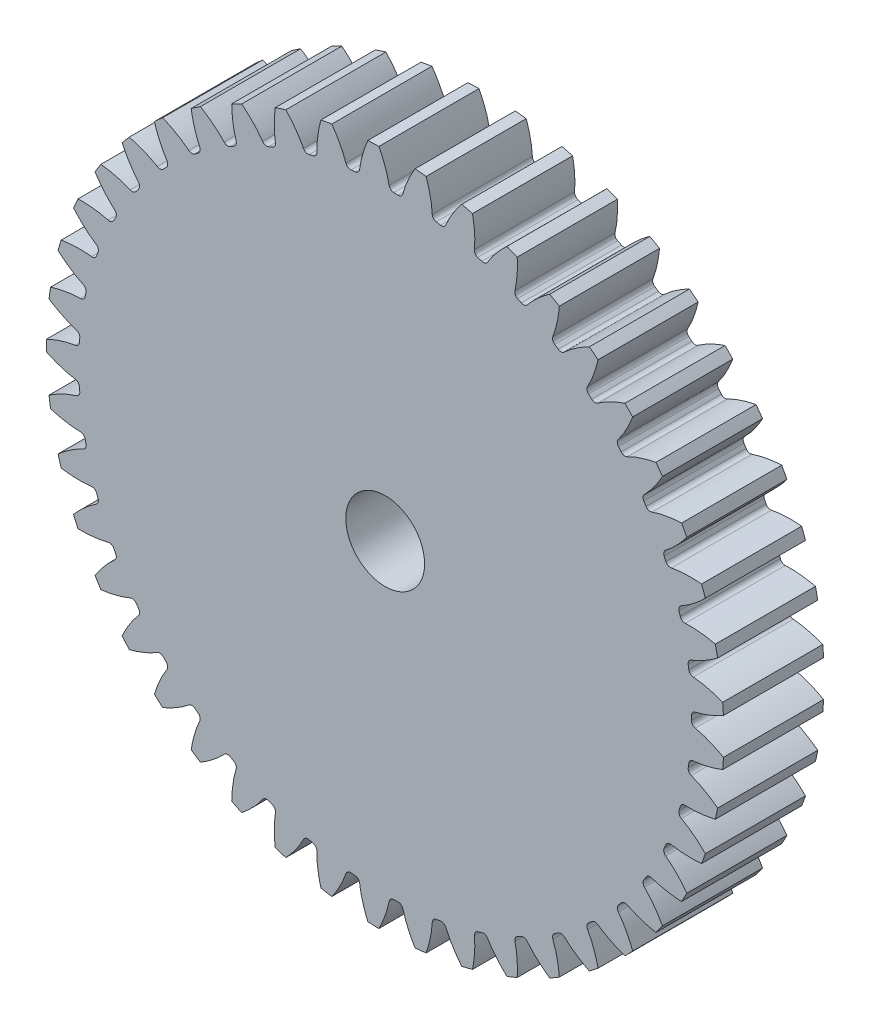
SolidWorks part; units mm, degrees
ref_plane "Front Plane" through (0, 0, 0) normal (0, 0, 1) x (1, 0, 0)
ref_plane "Top Plane" through (0, 0, 0) normal (0, 1, 0) x (1, 0, 0)
ref_plane "Right Plane" through (0, 0, 0) normal (1, 0, 0) x (0, 0, -1)
sketch "Sketch1" plane through (0, 0, 0) normal (0, 0, 1) x (1, 0, 0)
  circle A0 centre (0, 0) radius 21.486
  dimension "D1" = 42.9721
extrude "Boss-Extrude1" add sketch "Sketch1" against normal blind 6.35
sketch "Sketch2" plane through (0, 0, 0) normal (0, 0, 1) x (1, 0, 0)
  line L0 (19.3273, 0.3866) -> (19.425, 0.3886)
  line L1 (19.3273, -0.3866) -> (19.425, -0.3886)
  circle A0 centre (0, 0) radius 21.486
  circle A1 centre (0, 0) radius 19.3311
  circle A2 centre (0, 0) radius 20.5717
  circle A3 centre (0, 0) radius 19.4289
  spline S0 degree 4 poles (19.3273, 0.3866) (19.3364, 0.387) (19.362, 0.3884) (19.4104, 0.393) (19.489, 0.4032) (19.5888, 0.42) (19.7172, 0.4463) (19.8675, 0.4831) (20.0316, 0.5295) (20.2088, 0.5864) (20.3842, 0.6488) (20.5579, 0.7163) (20.7295, 0.7882) (20.9358, 0.8809) (21.1808, 0.9996) (21.4634, 1.1492) (21.7791, 1.3318) (22.0954, 1.5314) (22.402, 1.7388) (22.7059, 1.9608) (22.9958, 2.1844) (23.2906, 2.4289) (23.5594, 2.661) (23.853, 2.9344) (24.0877, 3.1589) (24.3889, 3.469) (24.5642, 3.6563) (24.7664, 3.8801) (24.8545, 3.982) (24.9089, 4.0446) knots 0 0 0 0 0 0.005377 0.015084 0.028532 0.04661 0.064855 0.092111 0.119476 0.146842 0.174209 0.201575 0.228941 0.256307 0.307035 0.361767 0.4165 0.471232 0.525964 0.580697 0.635429 0.690161 0.744894 0.799626 0.854358 0.909091 0.954545 1 1 1 1 1 construction
  spline S1 degree 4 poles (19.3273, 0.3866) (19.3364, 0.387) (19.362, 0.3884) (19.4104, 0.393) (19.489, 0.4032) (19.5888, 0.42) (19.7172, 0.4463) (19.8675, 0.4831) (20.0316, 0.5295) (20.2088, 0.5864) (20.3842, 0.6488) (20.5579, 0.7163) (20.7295, 0.7882) (20.9358, 0.8809) (21.1808, 0.9996) (21.4634, 1.1492) (21.7791, 1.3318) (22.0954, 1.5314) (22.402, 1.7388) (22.7059, 1.9608) (22.9958, 2.1844) (23.2906, 2.4289) (23.5594, 2.661) (23.853, 2.9344) (24.0877, 3.1589) (24.3236, 3.4018) (24.4374, 3.5216) (24.4952, 3.5834) knots 0 0 0 0 0 0.005377 0.015084 0.028532 0.04661 0.064855 0.092111 0.119476 0.146842 0.174209 0.201575 0.228941 0.256307 0.307035 0.361767 0.4165 0.471232 0.525964 0.580697 0.635429 0.690161 0.744894 0.799626 0.854358 0.909091 0.909091 0.909091 0.909091 0.909091
  spline S2 degree 4 poles (19.3273, -0.3866) (19.3364, -0.387) (19.362, -0.3884) (19.4104, -0.393) (19.489, -0.4032) (19.5888, -0.42) (19.7172, -0.4463) (19.8675, -0.4831) (20.0316, -0.5295) (20.2088, -0.5864) (20.3842, -0.6488) (20.5579, -0.7163) (20.7295, -0.7882) (20.9358, -0.8809) (21.1808, -0.9996) (21.4634, -1.1492) (21.7791, -1.3318) (22.0954, -1.5314) (22.402, -1.7388) (22.7059, -1.9608) (22.9958, -2.1844) (23.2906, -2.4289) (23.5594, -2.661) (23.853, -2.9344) (24.0877, -3.1589) (24.3889, -3.469) (24.5642, -3.6563) (24.7664, -3.8801) (24.8545, -3.982) (24.9089, -4.0446) knots 0 0 0 0 0 0.005377 0.015084 0.028532 0.04661 0.064855 0.092111 0.119476 0.146842 0.174209 0.201575 0.228941 0.256307 0.307035 0.361767 0.4165 0.471232 0.525964 0.580697 0.635429 0.690161 0.744894 0.799626 0.854358 0.909091 0.954545 1 1 1 1 1 construction
  spline S3 degree 4 poles (19.3273, -0.3866) (19.3364, -0.387) (19.362, -0.3884) (19.4104, -0.393) (19.489, -0.4032) (19.5888, -0.42) (19.7172, -0.4463) (19.8675, -0.4831) (20.0316, -0.5295) (20.2088, -0.5864) (20.3842, -0.6488) (20.5579, -0.7163) (20.7295, -0.7882) (20.9358, -0.8809) (21.1808, -0.9996) (21.4634, -1.1492) (21.7791, -1.3318) (22.0954, -1.5314) (22.402, -1.7388) (22.7059, -1.9608) (22.9958, -2.1844) (23.2906, -2.4289) (23.5594, -2.661) (23.853, -2.9344) (24.0877, -3.1589) (24.3236, -3.4018) (24.4374, -3.5216) (24.4952, -3.5834) knots 0 0 0 0 0 0.005377 0.015084 0.028532 0.04661 0.064855 0.092111 0.119476 0.146842 0.174209 0.201575 0.228941 0.256307 0.307035 0.361767 0.4165 0.471232 0.525964 0.580697 0.635429 0.690161 0.744894 0.799626 0.854358 0.909091 0.909091 0.909091 0.909091 0.909091
  dimension "D2" = 38.6622
  dimension "D3" = 42.9721
  dimension "D4" = 41.1435
  dimension "D1" = 38.8578
extrude "Cut-Extrude1" cut sketch "Sketch2" against normal up to next contours A2 S3 A0 S1 | A3 S3 A2 S1 region at (20.0564, 0, 0) region at (21.0574, 0, 0)
fillet "Fillet1" radius 0.3068 2 edges at (19.4249, -0.3952, -3.175) (19.4249, 0.3952, -3.175)
pattern_circular "CirPattern1" count 45 over 360 about axis through (0, 0, 0) along (0, 0, 1) of "Cut-Extrude1", "Fillet1"
sketch "Sketch4" plane through (0, 0, 0) normal (0, 0, 1) x (1, 0, 0)
  circle A0 centre (0, 0) radius 2.5
  dimension "D1" = 5
extrude "Cut-Extrude2" cut sketch "Sketch4" against normal up to next
equation "\"Module\"= .9143'module = 25.4/PD"
equation "\"DiametralPitch\"= 25.4 / \"Module\"'DP=25.4/module"
equation "\"NumTeeth\" = 45"
equation "\"PressureAngle\"= 20"
equation "\"Addendum\"= 1 / \"DiametralPitch\""
equation "\"Dedendum\"= 1.25 / \"DiametralPitch\""
equation "\"WorkingDepth\"= 2 / \"DiametralPitch\""
equation "\"WholeDepth\"= 2.25 / \"DiametralPitch\""
equation "\"Clearance\"= 0.25 / \"DiametralPitch\""
equation "\"ToothThickness\"= 1.5708 / \"DiametralPitch\""
equation "\"CircularPitch\"= pi / \"DiametralPitch\""
equation "\"PitchCircle\"= \"NumTeeth\" / \"DiametralPitch\""
equation "\"OutsideDiameter\"= ( \"NumTeeth\" + 2 ) / \"DiametralPitch\""
equation "\"Fillet\"= \"Clearance\" * cos ( \"PressureAngle\" ) * tan ( ( 90 + \"PressureAngle\" ) / 2 )"
equation "\"AddendumCircle\"= \"PitchCircle\" + ( 2 * \"Addendum\" )"
equation "\"DedendumCircle\"= \"PitchCircle\" - ( 2 * \"Dedendum\" )"
equation "\"BaseCircle\"= \"PitchCircle\" * cos ( \"PressureAngle\" )"
equation "\"PitchAngle\"= 360deg / \"NumTeeth\""
equation "\"Alpha\"= sqr ( \"PitchCircle\" ^ 2 - \"BaseCircle\" ^ 2 ) / \"BaseCircle\" * 180 / PI - \"PressureAngle\""
equation "\"Beta\"= ( \"PitchAngle\" / 4 - \"Alpha\" )"
equation "\"Phi\"= sqr ( ( \"AddendumCircle\" / 2 ) ^ 2 - ( \"BaseCircle\" / 2 ) ^ 2 ) / ( \"BaseCircle\" / 2 )"
equation "\"D1@Sketch1\"=\"OutsideDiameter\""
equation "\"D2@Sketch2\"=\"BaseCircle\""
equation "\"D3@Sketch2\"=\"AddendumCircle\""
equation "\"D4@Sketch2\"=\"PitchCircle\""
equation "\"D1@CirPattern1\"=\"NumTeeth\""
equation "\"D1@Fillet1\"=\"Fillet\""
equation "\"D1@Sketch2\"=\"DedendumCircle\""
